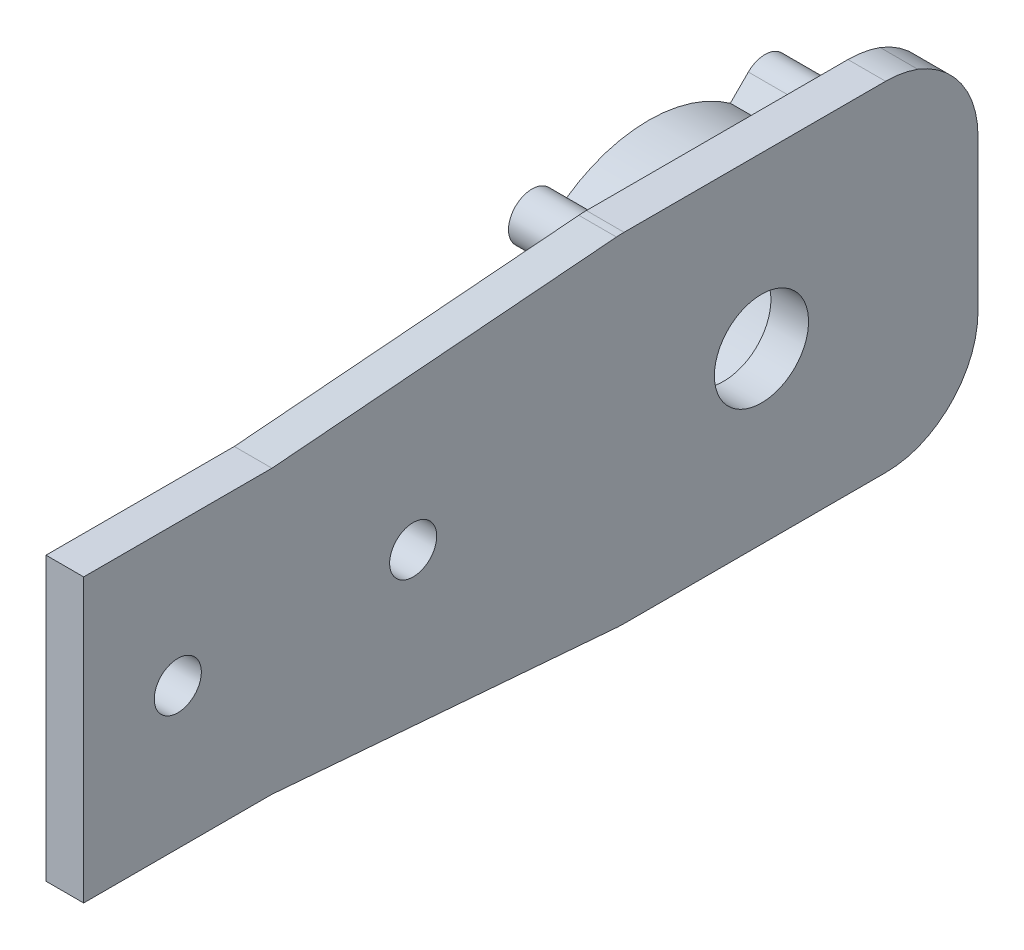
SolidWorks part; units mm, degrees
ref_plane "Front Plane" through (0, 0, 0) normal (0, 0, 1) x (1, 0, 0)
ref_plane "Top Plane" through (0, 0, 0) normal (0, 1, 0) x (1, 0, 0)
ref_plane "Right Plane" through (0, 0, 0) normal (1, 0, 0) x (0, 0, -1)
sketch "Sketch1" plane through (0, 0, 0) normal (0, 1, 0) x (1, 0, 0)
  line L2 (18, 31) -> (18, -44)
  line L6 (18, -44) -> (14, -44)
  line L8 (14, -44) -> (14, 31)
  line L9 (14, 31) -> (18, 31)
  dimension "D3" = 75
extrude "Boss-Extrude1" add sketch "Sketch1" along normal blind 30
sketch "Sketch4" plane through (14, 0, 0) normal (-1, 0, 0) x (0, 0, 1)
  line L0 (44, 30) -> (44, 0) construction
  line L1 (-8, 15) -> (-8, 10.2623) construction
  line L4 (-22.1421, 25.6066) -> (-20.226, 23.6905)
  line L5 (-18.6066, 29.1421) -> (-16.6905, 27.226)
  line L8 (2.6066, 29.1421) -> (0.6905, 27.226)
  line L9 (6.1421, 25.6066) -> (4.226, 23.6905)
  line L12 (6.1421, 4.3934) -> (4.226, 6.3095)
  line L13 (2.6066, 0.8579) -> (0.6905, 2.774)
  line L16 (-18.6066, 0.8579) -> (-16.6905, 2.774)
  line L17 (-22.1421, 4.3934) -> (-20.226, 6.3095)
  arc A1 (-20.226, 23.6905) -> (-20.226, 6.3095) centre (-8, 15) ccw
  arc A5 (-22.1421, 25.6066) -> (-18.6066, 29.1421) centre (-20.3744, 27.3744) cw
  circle A6 centre (-20.3744, 27.3744) radius 0.5
  circle A7 centre (-8, 15) radius 11.3
  arc A9 (2.6066, 29.1421) -> (6.1421, 25.6066) centre (4.3744, 27.3744) cw
  circle A10 centre (4.3744, 27.3744) radius 0.5
  arc A13 (6.1421, 4.3934) -> (2.6066, 0.8579) centre (4.3744, 2.6256) cw
  circle A14 centre (4.3744, 2.6256) radius 0.5
  arc A17 (-18.6066, 0.8579) -> (-22.1421, 4.3934) centre (-20.3744, 2.6256) cw
  circle A18 centre (-20.3744, 2.6256) radius 0.5
  arc A20 (0.6905, 27.226) -> (-16.6905, 27.226) centre (-8, 15) ccw
  arc A21 (4.226, 6.3095) -> (4.226, 23.6905) centre (-8, 15) ccw
  arc A22 (-16.6905, 2.774) -> (0.6905, 2.774) centre (-8, 15) ccw
  point P74 (-8, 15)
  dimension "D1" = 52
  dimension "D4" = 15
  dimension "D5" = 2.5
  dimension "D6" = 1
  dimension "D2" = 22.6
extrude "Boss-Extrude2" add sketch "Sketch4" along normal blind 8
sketch "Sketch5" plane through (14, 0, 0) normal (-1, 0, 0) x (0, 0, 1)
  line L0 (-31, 0) -> (-23, -3)
  line L1 (-23, 33) -> (7, 33)
  line L3 (-23, -3) -> (7, -3)
  line L5 (-23, 33) -> (7, -3) construction
  line L6 (-23, -3) -> (7, 33) construction
  line L7 (-31, 30) -> (-23, 33)
  line L8 (7, 33) -> (44, 30)
  line L9 (7, -3) -> (44, 0)
  line L10 (-31, 30) -> (-31, 0)
  line L12 (44, 30) -> (64, 30)
  line L13 (64, 30) -> (64, 0)
  line L14 (64, 0) -> (44, 0)
  point P0 (-8, 15)
  dimension "D1" = 36
  dimension "D2" = 30
  dimension "D3" = 20
extrude "Boss-Extrude3" add sketch "Sketch5" against normal blind 4
fillet "Fillet1" radius 10 6 edges at (16, 30, -31) (16, 0, -31) (16, 33, 7) (16, -3, 7) (16, 33, -23) (16, -3, -23)
sketch "Sketch9" plane through (14, 0, 0) normal (-1, 0, 0) x (0, 0, 1)
  line L0 (64, 0) -> (64, 30) construction
  circle A0 centre (54, 15) radius 2.5
  circle A1 centre (29, 15) radius 2.5
  circle A2 centre (-8, 15) radius 5
  dimension "D1" = 10
  dimension "D2" = 25
extrude "Cut-Extrude2" cut sketch "Sketch9" against normal blind 4
